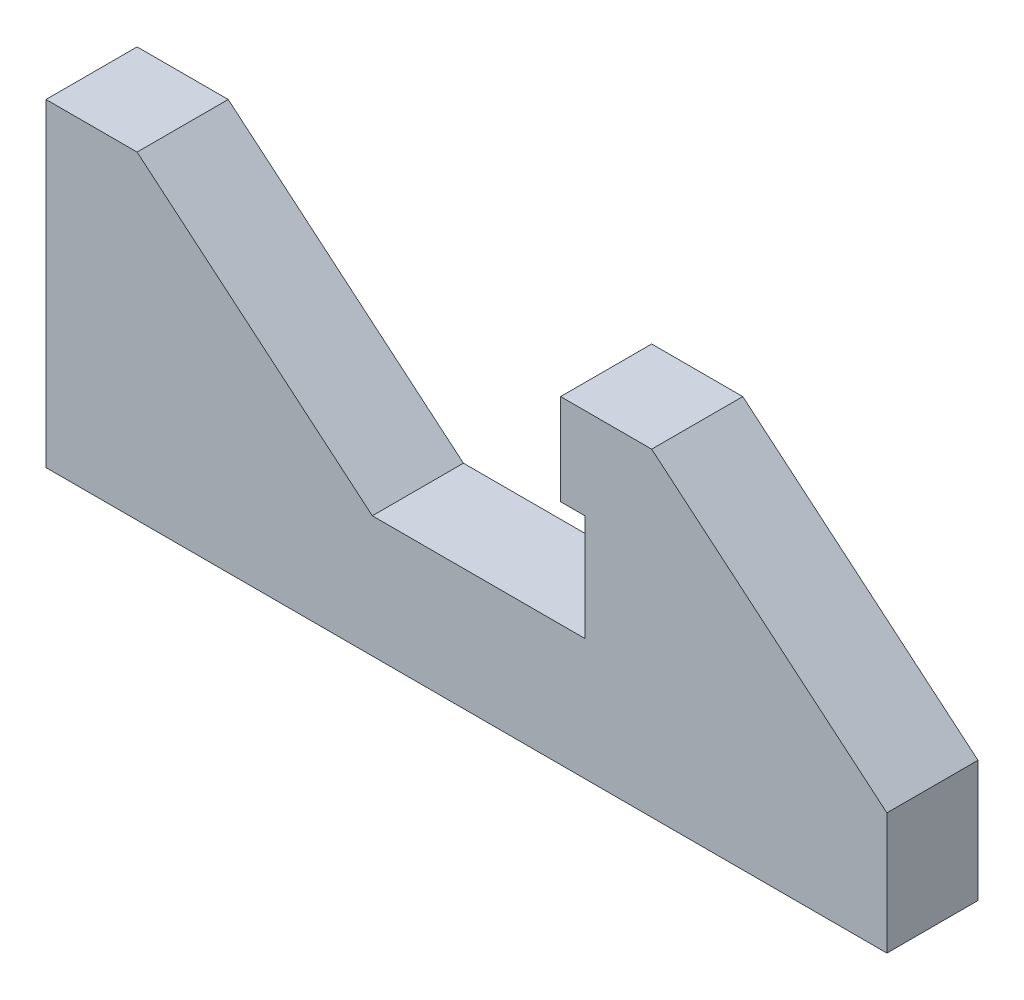
SolidWorks part; units mm, degrees
ref_plane "Front Plane" through (0, 0, 0) normal (0, 0, 1) x (1, 0, 0)
ref_plane "Top Plane" through (0, 0, 0) normal (0, 1, 0) x (1, 0, 0)
ref_plane "Right Plane" through (0, 0, 0) normal (1, 0, 0) x (0, 0, -1)
sketch "Sketch1" plane through (0, 0, 0) normal (0, 0, 1) x (1, 0, 0)
  line L0 (0, 0) -> (0, 105)
  line L1 (0, 105) -> (30, 105)
  line L2 (30, 105) -> (107.464, 40)
  line L3 (107.464, 40) -> (177.464, 40)
  line L4 (177.464, 40) -> (177.464, 75)
  line L5 (177.464, 75) -> (169.464, 75)
  line L6 (169.464, 75) -> (169.464, 105)
  line L7 (169.464, 105) -> (199.464, 105)
  line L8 (199.464, 105) -> (276.928, 40)
  line L9 (276.928, 40) -> (276.928, 0)
  line L10 (276.928, 0) -> (0, 0)
  point P3 (126.861, 40)
  point P13 (224.4796, 40)
  point P14 (0, 0)
  point P15 (30, 103.7139)
  dimension "D1" = 50
  dimension "D2" = 30
  dimension "D3" = 30
  dimension "D4" = 8
  dimension "D5" = 35
  dimension "D6" = 40
  dimension "D7" = 30
  dimension "D8" = 70
extrude "Boss-Extrude1" add sketch "Sketch1" along normal blind 30
